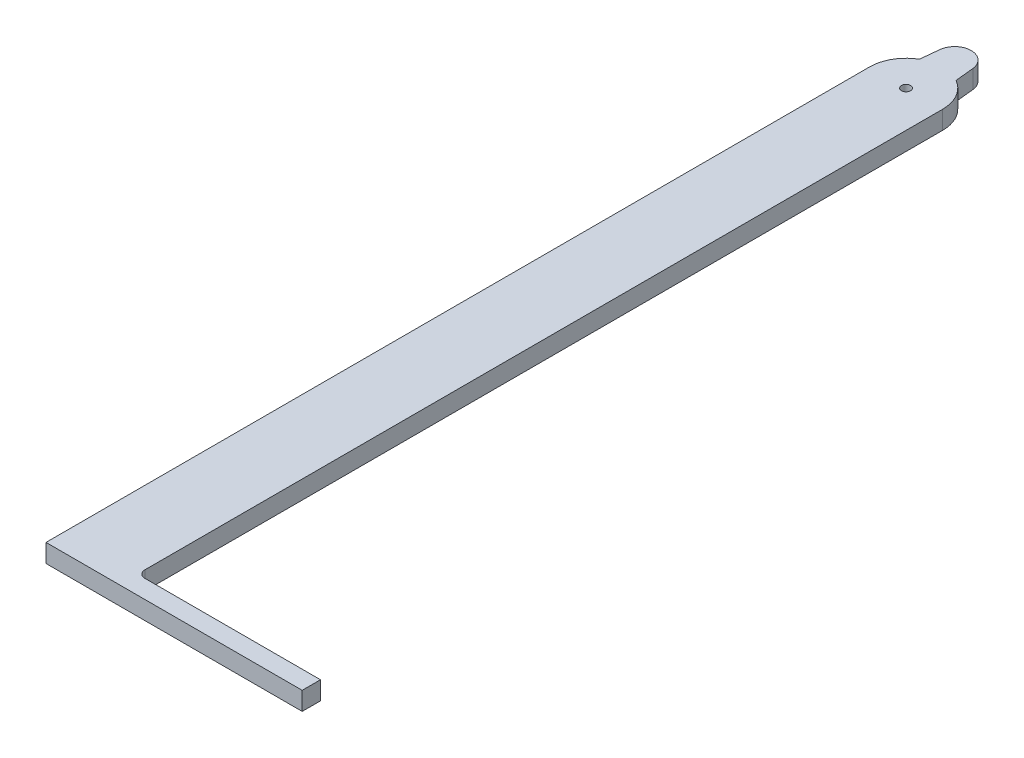
SolidWorks part; units mm, degrees
ref_plane "Front Plane" through (0, 0, 0) normal (0, 0, 1) x (1, 0, 0)
ref_plane "Top Plane" through (0, 0, 0) normal (0, 1, 0) x (1, 0, 0)
ref_plane "Right Plane" through (0, 0, 0) normal (1, 0, 0) x (0, 0, -1)
sketch "Sketch1" plane through (0, 0, 0) normal (0, 1, 0) x (1, 0, 0)
  line L1 (-12.7, 0) -> (12.7, 0)
  line L2 (-12.7, 0) -> (-12.7, -279.4)
  line L3 (-12.7, -279.4) -> (12.7, -279.4)
  line L4 (12.7, 0) -> (12.7, -279.4)
  circle A0 centre (0, 0) radius 12.7
  dimension "D1" = 25.4
  dimension "D2" = 279.4
extrude "Boss-Extrude1" add sketch "Sketch1" along normal blind 6.35 contours A0 L2 L3 L4 | L1 A0 | L1 A0 region at (0, 0, -5.39) region at (0, 0, 144.6724) region at (0, 0, 5.39)
sketch "Sketch2" plane through (0, 6.35, 0) normal (0, 1, 0) x (1, 0, 0)
  line L1 (-12.7, -279.4) -> (76.2, -279.4)
  line L2 (-12.7, -279.4) -> (-12.7, -285.75)
  line L3 (-12.7, -285.75) -> (76.2, -285.75)
  line L4 (76.2, -279.4) -> (76.2, -285.75)
  dimension "D1" = 88.9
  dimension "D2" = 6.35
extrude "Boss-Extrude2" add sketch "Sketch2" against normal up to surface (6.35 mm away) up to face at (0, 0, 136.525)
fillet "Fillet1" radius 2.54 1 edges
sketch "Sketch3" plane through (0, 0, 0) normal (0, -1, 0) x (-1, 0, 0)
  line L4 (-7.3841, 1.2138) -> (7.3841, 1.2138)
  line L6 (-7.3841, 1.2138) -> (-5.6981, 17.4684)
  line L7 (5.6981, 17.4684) -> (7.3841, 1.2138)
  line L8 (-7.3841, 1.2138) -> (-5.6981, 17.4684)
  line L9 (5.6981, 17.4684) -> (7.3841, 1.2138)
  arc A3 (5.6981, 17.4684) -> (-5.6981, 17.4684) centre (0, 16.8774) ccw
  arc A4 (5.6981, 17.4684) -> (-5.6981, 17.4684) centre (0, 16.8774) ccw
  dimension "D1" = 3.175
extrude "Boss-Extrude3" add sketch "Sketch3" against normal up to surface (6.35 mm away) up to face at (28.2277, 6.35, 179.508)
sketch "Sketch4" plane through (0, 0, 0) normal (0, -1, 0) x (-1, 0, 0)
  circle A0 centre (0, 0) radius 1.5875
  dimension "D1" = 3.175
extrude "Cut-Extrude1" cut sketch "Sketch4" against normal through all
